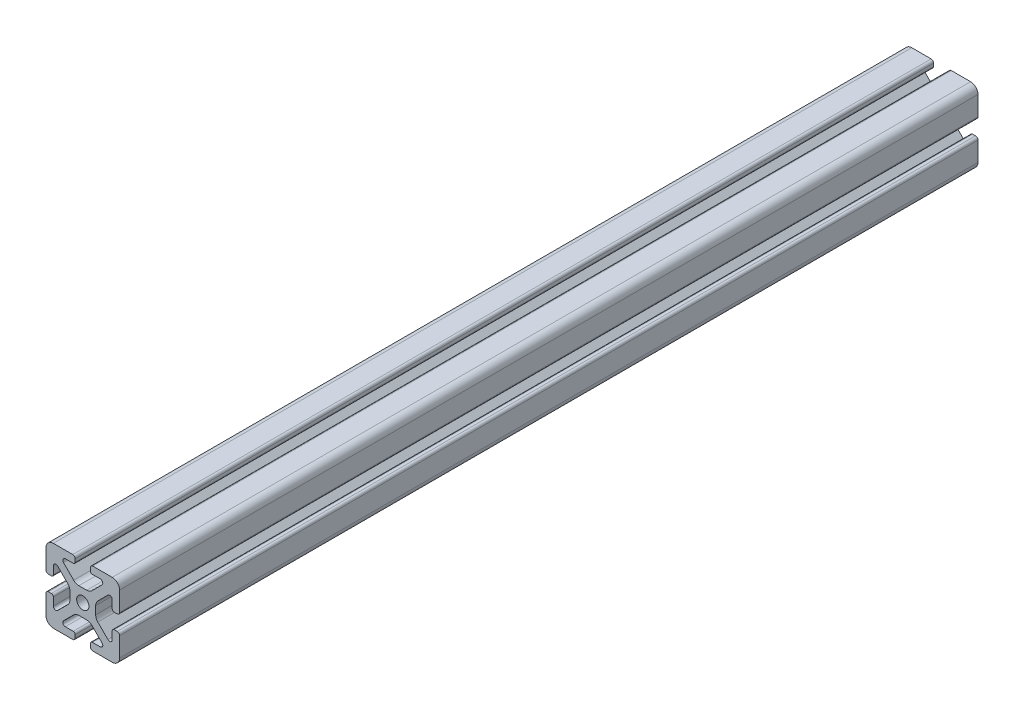
SolidWorks part; units mm, degrees
material "3003 Alloy"
ref_plane "Front Plane" through (0, 0, 0) normal (0, 0, 1) x (1, 0, 0)
ref_plane "Top Plane" through (0, 0, 0) normal (0, 1, 0) x (1, 0, 0)
ref_plane "Right Plane" through (0, 0, 0) normal (1, 0, 0) x (0, 0, -1)
sketch "Sketch1" plane through (0, 0, 0) normal (0, 0, 1) x (1, 0, 0)
  line B0 (1.6032, 5.25) -> (-1.6032, 5.25)
  arc B1 (-12, 15) -> (-15, 12) centre (-12, 12) ccw
  line B2 (-7.1276, 12) -> (-3.9, 12)
  line B3 (7.8506, 10.2547) -> (3.7245, 6.1287)
  line B4 (-10.2547, 7.8506) -> (-6.1287, 3.7245)
  line B5 (3.1, -12.8) -> (3.1, -14)
  arc B6 (3.9, -12) -> (3.1, -12.8) centre (3.9, -12.8) ccw
  line B7 (7.1276, -12) -> (3.9, -12)
  arc B8 (7.1276, -12) -> (7.8506, -10.2547) centre (7.1276, -10.9776) ccw
  line B9 (3.7245, -6.1287) -> (7.8506, -10.2547)
  arc B10 (3.7245, -6.1287) -> (1.6032, -5.25) centre (1.6032, -8.25) ccw
  line B11 (-1.6032, -5.25) -> (1.6032, -5.25)
  arc B12 (-1.6032, -5.25) -> (-3.7245, -6.1287) centre (-1.6032, -8.25) ccw
  line B13 (-7.8506, -10.2547) -> (-3.7245, -6.1287)
  arc B14 (-7.8506, -10.2547) -> (-7.1276, -12) centre (-7.1276, -10.9776) ccw
  line B15 (-3.9, -12) -> (-7.1276, -12)
  arc B16 (-3.1, -12.8) -> (-3.9, -12) centre (-3.9, -12.8) ccw
  line B17 (-3.1, -14) -> (-3.1, -12.8)
  arc B18 (-4.1, -15) -> (-3.1, -14) centre (-4.1, -14) ccw
  line B19 (-12, -15) -> (-4.1, -15)
  arc B20 (-15, -12) -> (-12, -15) centre (-12, -12) ccw
  line B21 (-15, -4.1) -> (-15, -12)
  arc B22 (-14, -3.1) -> (-15, -4.1) centre (-14, -4.1) ccw
  line B23 (-12.8, -3.1) -> (-14, -3.1)
  arc B24 (-12, -3.9) -> (-12.8, -3.1) centre (-12.8, -3.9) ccw
  line B25 (-12, -7.1276) -> (-12, -3.9)
  arc B26 (-12, -7.1276) -> (-10.2547, -7.8506) centre (-10.9776, -7.1276) ccw
  line B27 (-6.1287, -3.7245) -> (-10.2547, -7.8506)
  arc B28 (-6.1287, -3.7245) -> (-5.25, -1.6032) centre (-8.25, -1.6032) ccw
  line B29 (-5.25, 1.6032) -> (-5.25, -1.6032)
  arc B30 (-5.25, 1.6032) -> (-6.1287, 3.7245) centre (-8.25, 1.6032) ccw
  arc B31 (-10.2547, 7.8506) -> (-12, 7.1276) centre (-10.9776, 7.1276) ccw
  line B32 (-12, 3.9) -> (-12, 7.1276)
  arc B33 (-12.8, 3.1) -> (-12, 3.9) centre (-12.8, 3.9) ccw
  line B34 (-14, 3.1) -> (-12.8, 3.1)
  arc B35 (-15, 4.1) -> (-14, 3.1) centre (-14, 4.1) ccw
  line B36 (-15, 12) -> (-15, 4.1)
  line B37 (-4.1, 15) -> (-12, 15)
  arc B38 (-3.1, 14) -> (-4.1, 15) centre (-4.1, 14) ccw
  line B39 (-3.1, 12.8) -> (-3.1, 14)
  arc B40 (-3.9, 12) -> (-3.1, 12.8) centre (-3.9, 12.8) ccw
  arc B41 (-7.1276, 12) -> (-7.8506, 10.2547) centre (-7.1276, 10.9776) ccw
  line B42 (-3.7245, 6.1287) -> (-7.8506, 10.2547)
  arc B43 (-3.7245, 6.1287) -> (-1.6032, 5.25) centre (-1.6032, 8.25) ccw
  arc B44 (1.6032, 5.25) -> (3.7245, 6.1287) centre (1.6032, 8.25) ccw
  arc B45 (7.8506, 10.2547) -> (7.1276, 12) centre (7.1276, 10.9776) ccw
  line B46 (3.9, 12) -> (7.1276, 12)
  arc B47 (3.1, 12.8) -> (3.9, 12) centre (3.9, 12.8) ccw
  line B48 (3.1, 14) -> (3.1, 12.8)
  arc B49 (4.1, 15) -> (3.1, 14) centre (4.1, 14) ccw
  line B50 (12, 15) -> (4.1, 15)
  arc B51 (15, 12) -> (12, 15) centre (12, 12) ccw
  line B52 (15, 4.1) -> (15, 12)
  arc B53 (14, 3.1) -> (15, 4.1) centre (14, 4.1) ccw
  line B54 (12.8, 3.1) -> (14, 3.1)
  arc B55 (12, 3.9) -> (12.8, 3.1) centre (12.8, 3.9) ccw
  line B56 (12, 7.1276) -> (12, 3.9)
  arc B57 (12, 7.1276) -> (10.2547, 7.8506) centre (10.9776, 7.1276) ccw
  line B58 (6.1287, 3.7245) -> (10.2547, 7.8506)
  arc B59 (6.1287, 3.7245) -> (5.25, 1.6032) centre (8.25, 1.6032) ccw
  line B60 (5.25, -1.6032) -> (5.25, 1.6032)
  arc B61 (5.25, -1.6032) -> (6.1287, -3.7245) centre (8.25, -1.6032) ccw
  line B62 (10.2547, -7.8506) -> (6.1287, -3.7245)
  arc B63 (10.2547, -7.8506) -> (12, -7.1276) centre (10.9776, -7.1276) ccw
  line B64 (12, -3.9) -> (12, -7.1276)
  arc B65 (12.8, -3.1) -> (12, -3.9) centre (12.8, -3.9) ccw
  line B66 (14, -3.1) -> (12.8, -3.1)
  arc B67 (15, -4.1) -> (14, -3.1) centre (14, -4.1) ccw
  line B68 (15, -12) -> (15, -4.1)
  arc B69 (12, -15) -> (15, -12) centre (12, -12) ccw
  line B70 (4.1, -15) -> (12, -15)
  arc B71 (3.1, -14) -> (4.1, -15) centre (4.1, -14) ccw
  circle B72 centre (0, 0) radius 2.5
sketch_block_instance "IR 30X30 IR41901-2"
sketch_block "IR 30X30 IR41901"
extrude "Boss-Extrude1" add sketch "Sketch1" along normal blind 350
